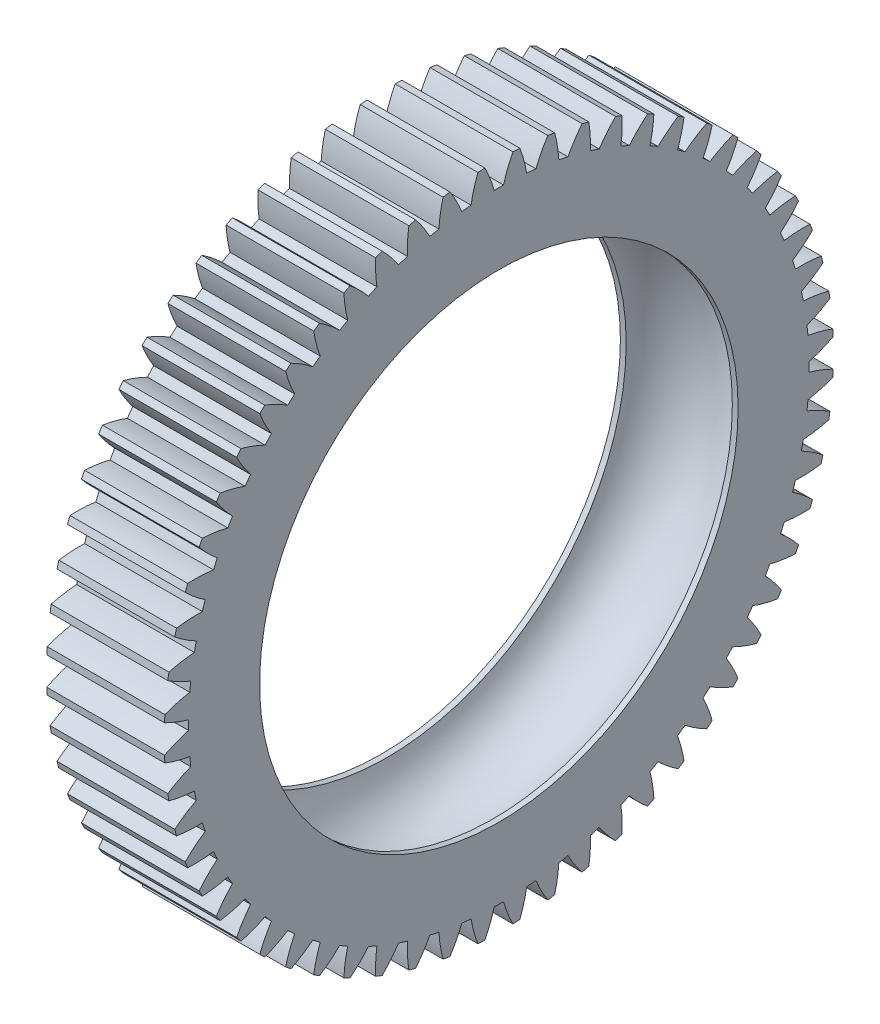
SolidWorks part; units mm, degrees
ref_plane "Plane1" through (0, 0, 0) normal (0, 0, 1) x (1, 0, 0)
ref_plane "Plane2" through (0, 0, 0) normal (0, 1, 0) x (1, 0, 0)
ref_plane "Plane3" through (0, 0, 0) normal (1, 0, 0) x (0, 0, -1)
other "Configuration Table"
sketch "HoldingSke" plane through (0, 0, 0) normal (0, 1, 0) x (1, 0, 0)
  line L0 (0, 0) -> (1, -1.7321)
  line L1 (-15, 0) -> (100, 0) construction
  line L2 (0, 0) -> (-2.1039, 2.3779)
  line L3 (0, 0) -> (-11.863, 4.5341)
  line L4 (0, 0) -> (4.318, 7.479)
  line L5 (0, 0) -> (-46.8476, -17.4728)
  line L6 (0, 0) -> (-5.8027, -3.9151)
  line L7 (-2.1039, 2.3779) -> (8.6586, 51.2059)
  line L8 (-76.2, 54.61) -> (-73.4, 54.61)
  line L9 (-71.009, 38.7566) -> (-53.1078, 45.2721)
  line L10 (-76.2, 71.12) -> (104.1128, 71.12)
  line L11 (0, 0) -> (-7, 0)
  line L12 (-76.2, 101.6) -> (-76.181, 101.6)
  line L13 (24.9733, 27.94) -> (52.9518, 28.4284)
  line L14 (24.9733, 27.94) -> (24.9743, 27.94)
  line L15 (24.9733, 27.94) -> (100.4006, 29.5858)
  line L16 (-63.627, -0.5) -> (-12.827, -0.5)
  circle A0 centre (0, 0) radius 10
  circle A1 centre (0, 0) radius 14.374
  circle A2 centre (0, 0) radius 37.5
  circle A3 centre (0, 0) radius 10
  dimension "Num_teeth" = 60
  dimension "Pitch_radius" = 180.3128
  dimension "Width" = 7
  dimension "Thickness" = 7
sketch "BasProSke" plane through (0, 0, 0) normal (0, 1, 0) x (1, 0, 0)
  line L0 (-10, 0) -> (60, 0) construction
  line L1 (0, 0) -> (0, 15.5)
  line L2 (0, 0) -> (7, 0)
  line L3 (7, 0) -> (7, 15.5)
  line L4 (7, 15.5) -> (0, 15.5)
  dimension "Thickness" = 7
  dimension "Diameter" = 31
revolve "Base-Revolve" add sketch "BasProSke" angle 360 about L0
sketch "TooCutSke" plane through (0, 0, 0) normal (1, 0, 0) x (0, 0, -1)
  line L1 (0, 0) -> (0, 107) construction
  line L2 (0, 0) -> (-0.4259, 14.994) construction
  line L3 (0, 0) -> (-1.5696, 29.9503) construction
  line L4 (-0.4259, 14.994) -> (-0.7848, 14.9751) construction
  arc A0 (0.2149, 14.3724) -> (-0.2149, 14.3724) centre (0, 0) ccw
  arc A1 (0.6627, 15.5112) -> (-0.6627, 15.5112) centre (0, 0) ccw
  circle A2 centre (0, 0) radius 15 construction
  circle A3 centre (0, 0) radius 14.0954 construction
  arc A4 (-0.2149, 14.3724) -> (-0.6627, 15.5112) centre (-5.9936, 12.7576) ccw
  arc A5 (0.6627, 15.5112) -> (0.2149, 14.3724) centre (5.9936, 12.7576) ccw
extrude "ToothCut" cut sketch "TooCutSke" along normal through all
fillet "Breaks" [suppressed] radius 0.01 tangent propagation no
fillet "RootFillets" [suppressed] radius 0.126
pattern_circular "TeethCuts" count 60 every 6 about axis through (-10, 0, 0) along (1, 0, 0) of "ToothCut", "RootFillets", "Breaks"
sketch "HubNeaOneSke" plane through (0, 0, 0) normal (-1, 0, 0) x (0, 0, 1)
  circle A0 centre (0, 0) radius 14.374
  dimension "Diameter" = 28.748
extrude "HubNearOne" [suppressed] add sketch "HubNeaOneSke" along normal blind 43.0001
sketch "HubNeaBotSke" plane through (0, 0, 0) normal (-1, 0, 0) x (0, 0, 1)
  circle A0 centre (0, 0) radius 14.374
  dimension "Diameter" = 28.748
extrude "HubNearBoth" [suppressed] add sketch "HubNeaBotSke" along normal blind 21.5
ref_plane "FarPln" through (7, 0, 0) normal (1, 0, 0) x (0, 0, -1)
sketch "HubFarSke" plane through (7, 0, 0) normal (1, 0, 0) x (0, 0, -1)
  circle A0 centre (0, 0) radius 14.374
  dimension "Diameter" = 28.748
extrude "HubFar" [suppressed] add sketch "HubFarSke" along normal blind 21.5
sketch "BorSke" plane through (0, 0, 0) normal (1, 0, 0) x (0, 0, -1)
  circle A0 centre (0, 0) radius 10
  dimension "Diameter" = 20
extrude "Bore" cut sketch "BorSke" along normal mid plane 100.0001
sketch "KeySke" plane through (0, 0, 0) normal (1, 0, 0) x (0, 0, -1)
  line L0 (-3, 0) -> (-3, 12.8)
  line L1 (-3, 12.8) -> (3, 12.8)
  line L2 (3, 12.8) -> (3, 0)
  line L3 (0, 0) -> (0, 34) construction
  line L4 (-3, 0) -> (3, 0)
  dimension "Width" = 6
extrude "Keyway" [suppressed] cut sketch "KeySke" along normal mid plane 100.0001
pattern_circular "Keyway2" [suppressed] count 2 every 90 about axis through (-10, 0, 0) along (1, 0, 0) reverse direction yes
scale "Scale1" bodies to scale 103 scale about centroid uniform scaling yes scale factor 0.97
sketch "Sketch1" plane through (6.895, 0, 0) normal (1, 0, 0) x (0, 0, -1)
  circle A0 centre (0, 0) radius 10
  dimension "D1" = 20
extrude "Cut-Extrude1" cut sketch "Sketch1" along normal blind 3 and the other way blind 31
ref_axis "Axis1" through (0.105, 0, 0) along (1, 0, 0)
ref_plane "Plane5" through (3.5, 0, 0) normal (1, 0, 0) x (0, 0, -1)
sketch "Sketch11" plane through (3.5, 0, 0) normal (1, 0, 0) x (0, 0, -1)
  circle A0 centre (0, 0) radius 10
  circle A1 centre (0, 0) radius 10 construction
sweep "Cut-Sweep2" cut path "Sketch11" circular profile diameter 5 parameters "D3"=5
sketch "Sketch19" plane through (6.895, 0, 0) normal (1, 0, 0) x (0, 0, -1)
  circle A0 centre (0, 0) radius 21.106
extrude "Cut-Extrude2" cut sketch "Sketch19" against normal blind 0.75
sketch "Sketch21" plane through (0.105, 0, 0) normal (-1, 0, 0) x (0, 0, 1)
  circle A0 centre (0, 0) radius 17.7632
extrude "Cut-Extrude3" cut sketch "Sketch21" against normal blind 0.75
sketch "Sketch23" plane through (6.145, 0, 0) normal (1, 0, 0) x (0, 0, -1)
  circle A0 centre (0, 0) radius 10.75
  dimension "D1" = 21.5
extrude "Cut-Extrude4" cut sketch "Sketch23" against normal blind 10
equation "' \"Module@HoldingSke\" = 6.35"
equation "' \"Num_teeth@HoldingSke\" = 12"
equation "' \"Ap@HoldingSke\" =  20"
equation "' \"Ap@HoldingSke\" = 20"
equation "' \"Width@HoldingSke\" = 0.5 * 25.4"
equation "' \"Hub_dia@HoldingSke\"= 1 * 25.4"
equation "' \"Hub_dia@HoldingSke\" = 1 * 25.4"
equation "' \"Overall_len@HoldingSke\" = 1.0 * 25.4"
equation "' \"Bore@HoldingSke\" = 0.75 * 25.4"
equation "' \"T_dim@HoldingSke\" = 0.1 * 25.4"
equation "' \"Width@KeySke\" = 0.25 * 25.4"
equation "' \"Show_teeth@HoldingSke\" = 13"
equation "' \"Backlash@HoldingSke\" = 0.009 * 25.4"
equation "' \"Addendum_fac@HoldingSke\" = 1.0"
equation "' \"Dedendum_fac@HoldingSke\" = 1.25"
equation "' \"Dedendum_add@HoldingSke\" = 0.00005 * 25.4"
equation "' \"Clearance_fac@HoldingSke\" = 0.25"
equation "\"Pitch@HoldingSke\" = 1 / \"Module@HoldingSke\""
equation "\"Overcut_dia@TooCutSke\" = (\"Num_teeth@HoldingSke\" + 2 * \"Addendum_fac@HoldingSke\") / \"Pitch@HoldingSke\" + 0.002 * 25.4"
equation "\"Pitch_dia@TooCutSke\" = \"Num_teeth@HoldingSke\" / \"Pitch@HoldingSke\""
equation "\"Base_dia@TooCutSke\" = \"Num_teeth@HoldingSke\" / \"Pitch@HoldingSke\" * cos((\"Ap@HoldingSke\"  * 3.14159265 / 180))"
equation "\"Root_dia@TooCutSke\" = (\"Num_teeth@HoldingSke\" + 2) / \"Pitch@HoldingSke\" - 2 * (\"Addendum_fac@HoldingSke\" + \"Dedendum_fac@HoldingSke\") / \"Pitch@HoldingSke\" - \"Dedendum_add@HoldingSke\" * 2"
equation "\"Half_ang@TooCutSke\" = 180 / \"Num_teeth@HoldingSke\""
equation "\"Half_CT@TooCutSke\" = \"Num_teeth@HoldingSke\" / \"Pitch@HoldingSke\" * sin((3.14159265 / 2 / \"Num_teeth@HoldingSke\")) / 2 - 7 * \"Backlash@HoldingSke\" / 4"
equation "\"Flank_rad@TooCutSke\" = \"Num_teeth@HoldingSke\" / \"Pitch@HoldingSke\" / 5"
equation "\"Radius@RootFillets\" = \"Clearance_fac@HoldingSke\" / \"Pitch@HoldingSke\" + \"Dedendum_add@HoldingSke\""
equation "\"Break_rad@Breaks\" = 0.02 / \"Pitch@HoldingSke\""
equation "\"Thickness@HoldingSke\" = \"Width@HoldingSke\""
equation "\"OAL@HoldingSke\" = \"Thickness@HoldingSke\""
equation "\"MHD@HoldingSke\" = (\"Num_teeth@HoldingSke\" + 2) / \"Pitch@HoldingSke\" - 2 * (\"Addendum_fac@HoldingSke\" + \"Dedendum_fac@HoldingSke\")  / \"Pitch@HoldingSke\" - \"Dedendum_add@HoldingSke\" * 2"
equation "\"MBD@HoldingSke\" = (\"Num_teeth@HoldingSke\" + 2) / \"Pitch@HoldingSke\" - 2 * (\"Addendum_fac@HoldingSke\" + \"Dedendum_fac@HoldingSke\")  / \"Pitch@HoldingSke\" - \"Dedendum_add@HoldingSke\" * 2 - 0.002 * 25.4"
equation "\"MHD@HoldingSke\" = ((sgn( \"MHD@HoldingSke\" - \"Hub_dia@HoldingSke\" )-1)*( \"MHD@HoldingSke\" - \"Hub_dia@HoldingSke\" ))/-2+ \"Hub_dia@HoldingSke\""
equation "\"MBD@HoldingSke\" = ((sgn( \"MBD@HoldingSke\" - \"Bore@HoldingSke\" )-1)*( \"MBD@HoldingSke\" - \"Bore@HoldingSke\" ))/-2+ \"Bore@HoldingSke\""
equation "\"OAL@HoldingSke\" = ((sgn( \"OAL@HoldingSke\" - \"Overall_len@HoldingSke\" )+1)*( \"OAL@HoldingSke\" - \"Overall_len@HoldingSke\" ))/2 + \"Overall_len@HoldingSke\" + 0.000002 * 25.4"
equation "\"Num_teeth@TeethCuts\" = int( \"Show_teeth@HoldingSke\" ) + 1"
equation "\"Num_teeth@TeethCuts\" = ((sgn( \"Num_teeth@TeethCuts\" - \"Num_teeth@HoldingSke\" )-1)*( \"Num_teeth@TeethCuts\" - \"Num_teeth@HoldingSke\" ))/-2+ \"Num_teeth@HoldingSke\""
equation "\"Num_teeth@TeethCuts\" = ((sgn( \"Num_teeth@TeethCuts\" - 2.0)+1)*( \"Num_teeth@TeethCuts\" - 2.0))/2 +2.0"
equation "\"Angle@TeethCuts\" = 360.0 / \"Num_teeth@HoldingSke\""
equation "\"Diameter@BasProSke\" = (\"Num_teeth@HoldingSke\" + 2 * \"Addendum_fac@HoldingSke\") / \"Pitch@HoldingSke\""
equation "\"Thickness@BasProSke\"  = \"Thickness@HoldingSke\""
equation "' \"Fillet_rad@BasProSke\" =  \"Thickness@HoldingSke\" * 0.05"
equation "' \"Fillet_rad@BasProSke\" = \"Thickness@HoldingSke\" * 0.05"
equation "\"MHD@HoldingSke\" = ((sgn( \"MHD@HoldingSke\" - \"Root_dia@TooCutSke\" )-1)*( \"MHD@HoldingSke\" - \"Root_dia@TooCutSke\" ))/-2+ \"Root_dia@TooCutSke\""
equation "\"Diameter@HubNeaOneSke\" = \"MHD@HoldingSke\""
equation "\"Length@HubNearOne\" = \"OAL@HoldingSke\" - \"Thickness@BasProSke\""
equation "\"Diameter@HubNeaBotSke\" = \"MHD@HoldingSke\""
equation "\"Length@HubNearBoth\" = ( \"OAL@HoldingSke\" - \"Thickness@BasProSke\" ) / 2.0"
equation "\"Thickness@FarPln\" = \"Thickness@BasProSke\""
equation "\"Diameter@HubFarSke\" = \"MHD@HoldingSke\""
equation "\"Length@HubFar\" = ( \"OAL@HoldingSke\" - \"Thickness@BasProSke\" ) / 2.0"
equation "\"Diameter@BorSke\" = \"MBD@HoldingSke\""
equation "\"D1@Bore\" = \"OAL@HoldingSke\" * 2.0"
equation "\"D1@Keyway\" = \"OAL@HoldingSke\" * 2.0"
equation "\"Offset@KeySke\" = \"T_dim@HoldingSke\" + \"MBD@HoldingSke\" / 2.0"
